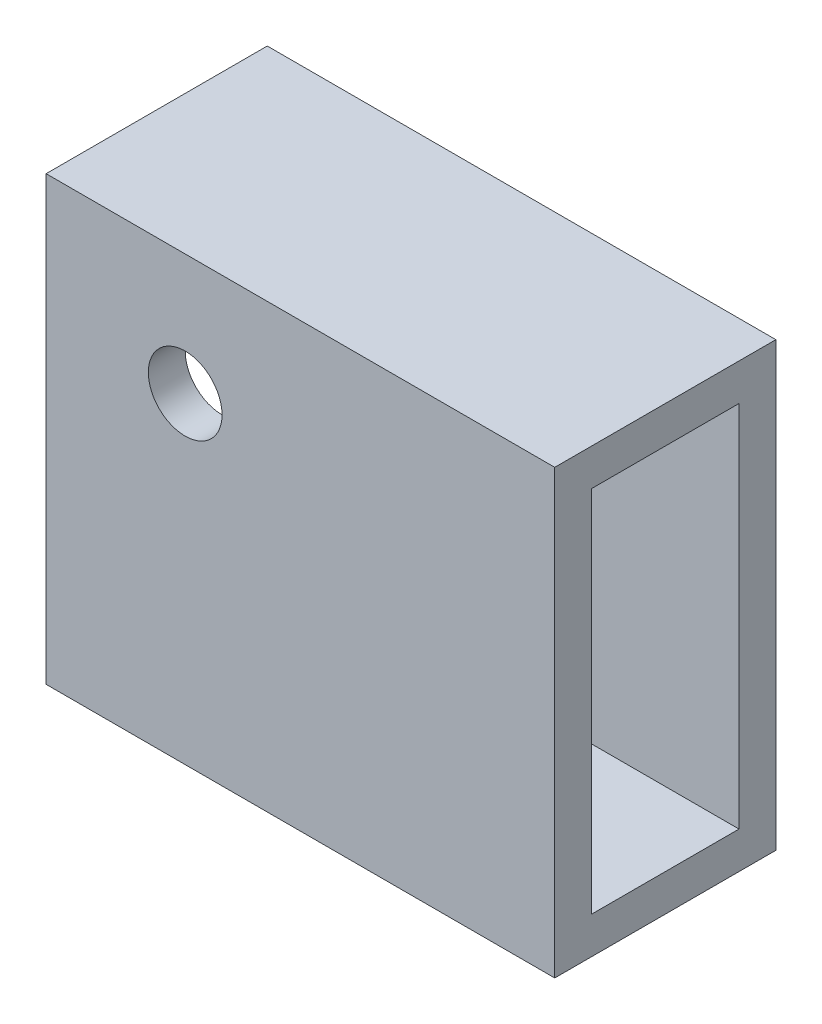
SolidWorks part; units mm, degrees
ref_plane "Front Plane" through (0, 0, 0) normal (0, 0, 1) x (1, 0, 0)
ref_plane "Top Plane" through (0, 0, 0) normal (0, 1, 0) x (1, 0, 0)
ref_plane "Right Plane" through (0, 0, 0) normal (1, 0, 0) x (0, 0, -1)
sketch "Sketch1" plane through (0, 0, 0) normal (0, 0, 1) x (1, 0, 0)
  line L4 (63.5, 38.1) -> (-63.5, 38.1)
  line L5 (63.5, -38.1) -> (63.5, 38.1)
  line L6 (-63.5, -38.1) -> (63.5, -38.1)
  line L7 (-63.5, 38.1) -> (-63.5, -38.1)
  line L8 (63.5, 38.1) -> (-63.5, 38.1)
  line L9 (63.5, -38.1) -> (63.5, 38.1)
  line L10 (-63.5, -38.1) -> (63.5, -38.1)
  line L11 (-63.5, 38.1) -> (-63.5, -38.1)
  circle A1 centre (25.4, 0) radius 12.7
  circle A2 centre (25.4, 0) radius 12.7
  dimension "D1" = 0
  dimension "D2" = 0
sketch "Sketch2" plane through (0, 0, 0) normal (0, 1, 0) x (1, 0, 0)
  line L4 (-63.5, 12.7) -> (-63.5, -25.4)
  line L5 (-63.5, -25.4) -> (63.5, -25.4)
  line L6 (63.5, -25.4) -> (63.5, 0)
  line L7 (-18.5941, 12.7) -> (-63.5, 12.7)
  line L8 (-63.5, 12.7) -> (-63.5, -25.4)
  line L9 (-63.5, -25.4) -> (63.5, -25.4)
  line L10 (63.5, -25.4) -> (63.5, 0)
  line L11 (-18.5941, 12.7) -> (-63.5, 12.7)
  arc A3 (63.5, 0) -> (25.4, 38.1) centre (25.4, 0) ccw
  arc A4 (25.4, 38.1) -> (-7.5956, 19.05) centre (25.4, 0) ccw
  arc A5 (-18.5941, 12.7) -> (-7.5956, 19.05) centre (-18.5941, 25.4) ccw
  arc A6 (63.5, 0) -> (25.4, 38.1) centre (25.4, 0) ccw
  arc A7 (25.4, 38.1) -> (-7.5956, 19.05) centre (25.4, 0) ccw
  arc A8 (-18.5941, 12.7) -> (-7.5956, 19.05) centre (-18.5941, 25.4) ccw
  dimension "D1" = 0
sketch "Sketch3" plane through (0, 0, 0) normal (0, 1, 0) x (1, 0, 0)
  line L0 (25.4, 88.9) -> (25.4, -76.2) construction
  line L1 (25.4, 88.9) -> (25.4, -76.2)
sketch "Sketch4" plane through (-152.4, 0, 0) normal (-1, 0, 0) x (0, 0, 1)
  line L8 (19.05, 31.75) -> (-6.35, 31.75)
  line L9 (-6.35, 31.75) -> (-6.35, -31.75)
  line L10 (-6.35, -31.75) -> (19.05, -31.75)
  line L11 (19.05, -31.75) -> (19.05, 31.75)
  line L12 (19.05, 31.75) -> (-6.35, 31.75)
  line L13 (-6.35, 31.75) -> (-6.35, -31.75)
  line L14 (-6.35, -31.75) -> (19.05, -31.75)
  line L15 (19.05, -31.75) -> (19.05, 31.75)
  line L16 (-12.7, 38.1) -> (-12.7, -38.1)
  line L17 (-12.7, -38.1) -> (25.4, -38.1)
  line L18 (25.4, -38.1) -> (25.4, 38.1)
  line L19 (25.4, 38.1) -> (-12.7, 38.1)
  line L20 (-12.7, 38.1) -> (-12.7, -38.1)
  line L21 (-12.7, -38.1) -> (25.4, -38.1)
  line L22 (25.4, -38.1) -> (25.4, 38.1)
  line L23 (25.4, 38.1) -> (-12.7, 38.1)
  dimension "D1" = 1.27
  dimension "D2" = 0
extrude "Boss-Extrude1" add sketch "Sketch4" against normal offset from surface (87.63 mm away) 1.27
sketch "Sketch5" plane through (0, 0, 25.4) normal (0, 0, 1) x (1, 0, 0)
  line L0 (-152.4, 38.1) -> (-64.77, -38.1) construction
  circle A0 centre (-128.4413, 17.2663) radius 6.35
  dimension "D1" = 12.7
  dimension "D2" = 31.75
extrude "Cut-Extrude1" cut sketch "Sketch5" against normal through all
